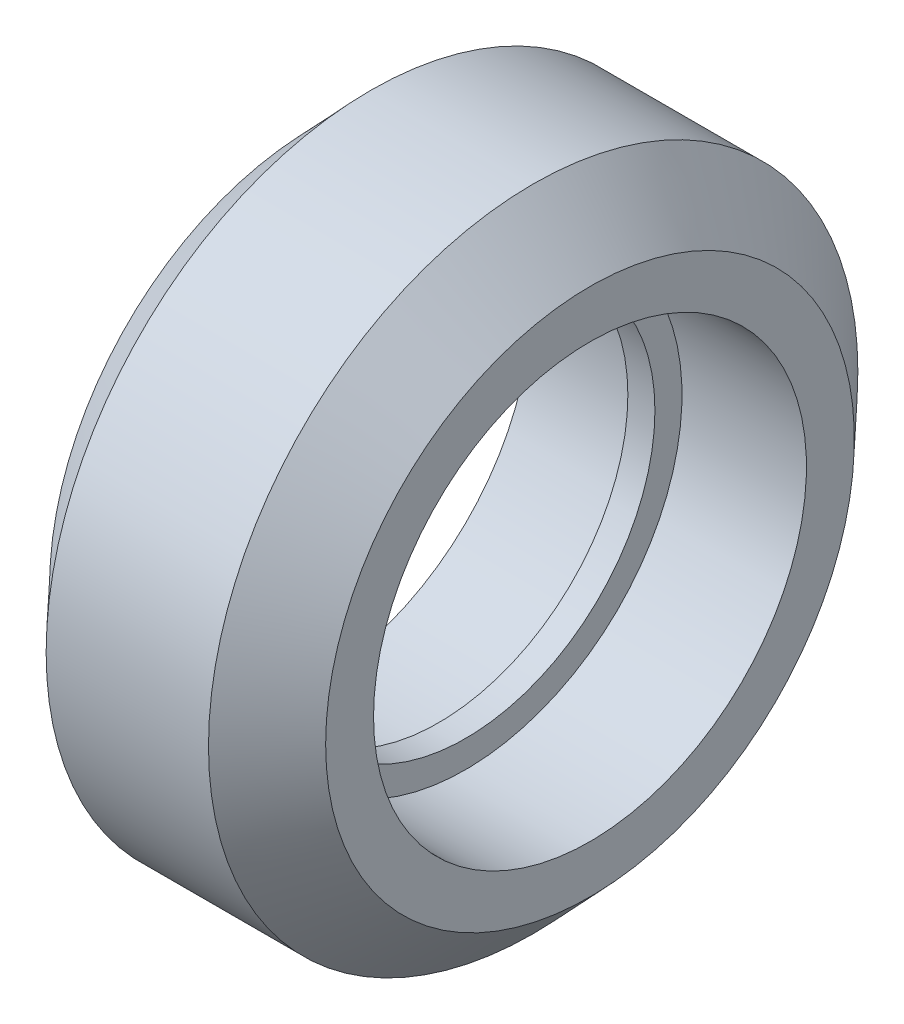
SolidWorks part; units mm, degrees
ref_plane "Front Plane" through (0, 0, 0) normal (0, 0, 1) x (1, 0, 0)
ref_plane "Top Plane" through (0, 0, 0) normal (0, 1, 0) x (1, 0, 0)
ref_plane "Right Plane" through (0, 0, 0) normal (1, 0, 0) x (0, 0, -1)
sketch "Sketch1" plane through (0, 0, 0) normal (0, 0, 1) x (1, 0, 0)
  line L0 (-3.4335, 0) -> (6.1117, 0) construction
  line L1 (0, 0) -> (0, 12) construction
  line L2 (-3, 12) -> (3, 12)
  line L3 (3, 12) -> (5.1, 9.77)
  line L4 (5.1, 9.77) -> (5.1, 8)
  line L5 (5.1, 8) -> (0.5, 8)
  line L6 (0.5, 8) -> (0.5, 7)
  line L7 (0.5, 7) -> (-0.5, 7)
  line L8 (-0.5, 8) -> (-0.5, 7)
  line L9 (-5.1, 8) -> (-0.5, 8)
  line L10 (-5.1, 9.77) -> (-5.1, 8)
  line L11 (-3, 12) -> (-5.1, 9.77)
  point P5 (5.1, 17.3411)
  point P13 (0, 7)
  dimension "D1" = 5.1
  dimension "D2" = 3
  dimension "D3" = 12
  dimension "D4" = 7
  dimension "D5" = 0.5
  dimension "D6" = 9.77
  dimension "D7" = 8
revolve "Revolve1" add sketch "Sketch1" angle 360 about L0
